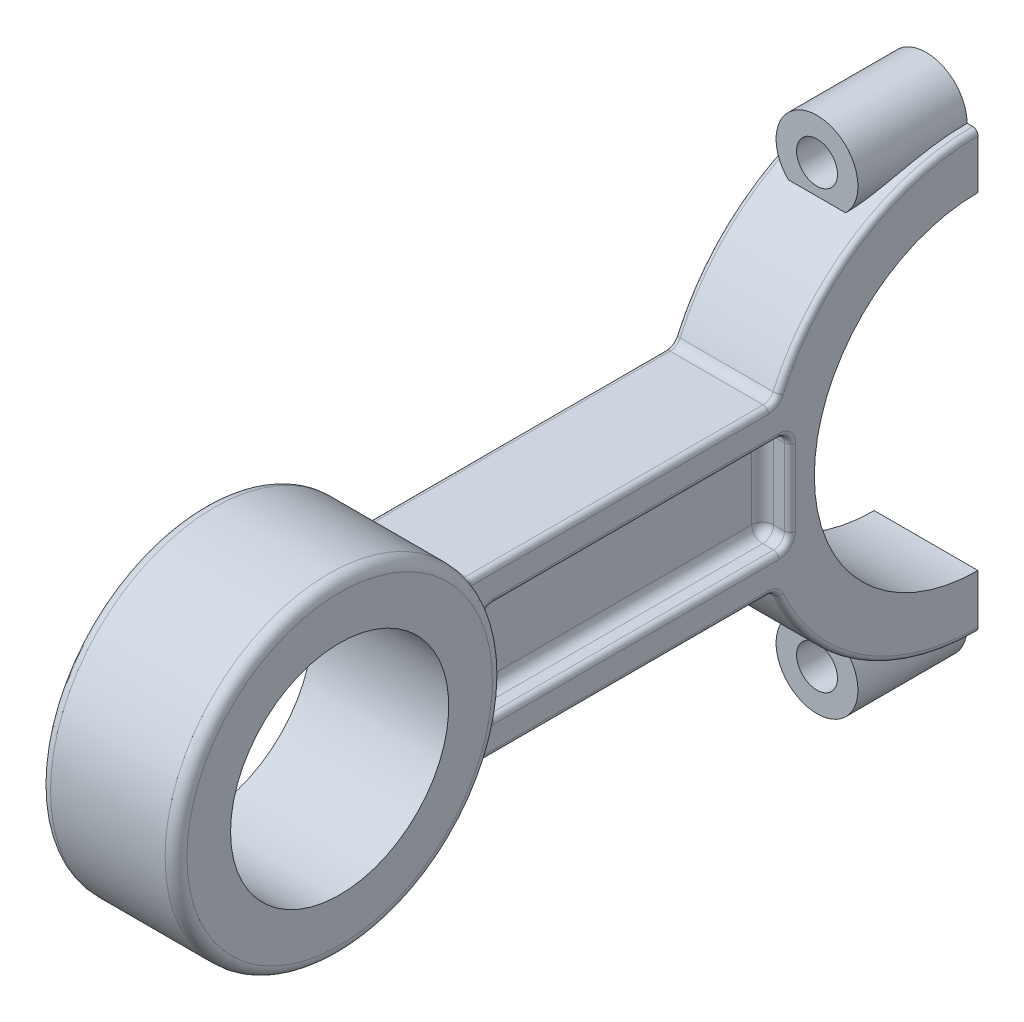
SolidWorks part; units mm, degrees
ref_plane "Front Plane" through (0, 0, 0) normal (0, 0, 1) x (1, 0, 0)
ref_plane "Top Plane" through (0, 0, 0) normal (0, 1, 0) x (1, 0, 0)
ref_plane "Right Plane" through (0, 0, 0) normal (1, 0, 0) x (0, 0, -1)
sketch "Sketch1" plane through (0, 0, 0) normal (1, 0, 0) x (0, 0, -1)
  line L0 (-76.2, 0) -> (76.2, 0) construction
  line L1 (76.2, 50.8) -> (76.2, 38.1)
  line L2 (29.1071, -19.05) -> (-59.3995, -19.05)
  line L4 (29.1071, 19.05) -> (-59.3995, 19.05)
  line L5 (-59.3995, -19.05) -> (-59.3995, 19.05) construction
  line L6 (59.3995, -19.05) -> (-59.3995, 19.05) construction
  line L7 (59.3995, 19.05) -> (-59.3995, -19.05) construction
  line L8 (76.2, -38.1) -> (76.2, -50.8)
  circle A0 centre (-76.2, 0) radius 25.4
  circle A1 centre (-76.2, 0) radius 38.1
  arc A2 (76.2, 38.1) -> (76.2, -38.1) centre (76.2, 0) ccw
  arc A3 (76.2, 50.8) -> (76.2, -50.8) centre (76.2, 0) ccw
  circle A4 centre (76.2, 0) radius 50.8 construction
  circle A5 centre (76.2, 0) radius 38.1 construction
  point P4 (0, 0)
  point P10 (0, 0)
  dimension "D2" = 50.8
  dimension "D4" = 76.2
  dimension "D1" = 152.4
  dimension "D6" = 38.1
  dimension "D3" = 12.7
  dimension "D5" = 12.7
extrude "Boss-Extrude1" add sketch "Sketch1" along normal mid plane 24.15 contours L4 A1 L2 A0 | L2 A1 L4 A0 | A3 L4 A1 L2 | L1 A3 L8 A2 region at (0, 44.45, -75.0641) region at (0, 0, 6.576) region at (0, 0, 46.7377) region at (0, 20.0922, 51.302)
extrude "Boss-Extrude2" add sketch "Sketch1<3>" along normal mid plane 31.75 contours A0 | A1
sketch "Sketch1<3>" plane through (0, 0, 0) normal (1, 0, 0) x (0, 0, -1) same geometry as "Sketch1"
sketch "Sketch2" plane through (0, 0, -76.2) normal (0, 0, -1) x (-1, 0, 0)
  line L0 (-12.075, -50.8) -> (12.075, -50.8) construction
  circle A0 centre (0, -50.8) radius 9.525
  dimension "D1" = 19.05
extrude "Boss-Extrude3" add sketch "Sketch2" against normal blind 25.4
sketch "Sketch3" plane through (0, 0, -76.2) normal (0, 0, -1) x (-1, 0, 0)
  circle A0 centre (0, -50.8) radius 4.76
  dimension "D1" = 9.52
extrude "Cut-Extrude1" cut sketch "Sketch3" against normal up to next
mirror "Mirror1" about plane through (0, 0, 0) normal (0, 1, 0) of "Boss-Extrude3", "Cut-Extrude1"
sketch "Sketch4" plane through (12.075, 0, 0) normal (1, 0, 0) x (0, 0, -1)
  line L0 (29.1071, 19.05) -> (-43.2044, 19.05) construction
  line L1 (32.4135, -11.43) -> (-39.8549, -11.43)
  line L2 (32.4135, -11.43) -> (32.4135, 11.43)
  line L3 (32.4135, 11.43) -> (-39.8549, 11.43)
  line L5 (32.4135, -11.43) -> (-39.8549, 11.43) construction
  line L6 (32.4135, 11.43) -> (-39.8549, -11.43) construction
  circle A0 centre (-76.2, 0) radius 38.1 construction
  arc A1 (-39.8549, -11.43) -> (-39.8549, 11.43) centre (-76.2, 0) ccw
  point P0 (-3.7207, 0)
  point P10 (28.6932, -11.43)
  point P11 (32.4135, -11.43)
  dimension "D1" = 7.62
extrude "Cut-Extrude2" cut sketch "Sketch4" against normal blind 6.35
mirror "Mirror2" about plane through (0, 0, 0) normal (1, 0, 0) of "Cut-Extrude2"
fillet "Fillet1" radius 2.54 22 edges at (-5.725, -11.43, 3.7207) (-5.725, 0, -32.4135) (-5.725, 11.43, 3.7207) (-5.725, 0, 38.1) (5.725, 11.43, 3.7207) (5.725, 0, -32.4135) (5.725, -11.43, 3.7207) (5.725, 0, 38.1) (-8.9, 11.43, -32.4135) (-8.9, -11.43, -32.4135) (-8.9, -11.43, 39.8549) (-8.9, 11.43, 39.8549) (8.9, 11.43, -32.4135) (8.9, -11.43, -32.4135) (8.9, 11.43, 39.8549) (8.9, -11.43, 39.8549) (0, -19.05, -29.1071) (0, -19.05, 43.2044) (0, 19.05, -29.1071) (0, 19.05, 43.2044) (15.875, 0, 38.1) (-15.875, 0, 38.1)
fillet "Fillet2" radius 1.27 14 edges at (12.075, -10.4775, 38.527) (12.075, -11.43, 3.3354) (12.075, -10.6861, -31.6695) (12.075, 0, -32.4135) (12.075, 10.6861, -31.6695) (12.075, 10.4775, 38.527) (-12.075, -10.4775, 38.527) (-12.075, 10.4775, 38.527) (-12.075, 11.43, 3.3354) (-12.075, 10.6861, -31.6695) (-12.075, 0, -32.4135) (-12.075, -10.6861, -31.6695) (12.075, 11.43, 3.3354) (-12.075, -11.43, 3.3354)
fillet "Fillet3" radius 1.25 16 edges at (-12.075, 42.5746, -48.4863) (-12.075, 19.4613, -28.8104) (-12.075, 19.3675, 42.9989) (-12.075, -42.5746, -48.4863) (-12.075, -19.4613, -28.8104) (-12.075, -19.3675, 42.9989) (12.075, 42.5746, -48.4863) (12.075, 19.4613, -28.8104) (12.075, 19.3675, 42.9989) (12.075, -42.5746, -48.4863) (12.075, -19.4613, -28.8104) (12.075, -19.3675, 42.9989) (-12.075, 19.05, 7.1722) (-12.075, -19.05, 7.1722) (12.075, 19.05, 7.1722) (12.075, -19.05, 7.1722)
